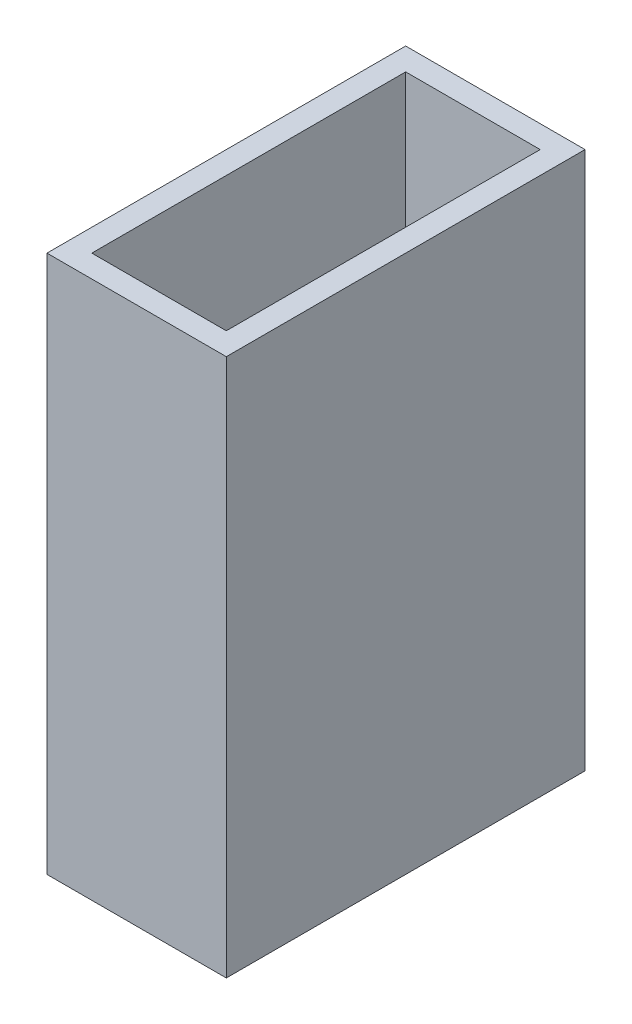
SolidWorks part; units mm, degrees
ref_plane "Front Plane" through (0, 0, 0) normal (0, 0, 1) x (1, 0, 0)
ref_plane "Top Plane" through (0, 0, 0) normal (0, 1, 0) x (1, 0, 0)
ref_plane "Right Plane" through (0, 0, 0) normal (1, 0, 0) x (0, 0, -1)
sketch "Sketch1" plane through (0, 0, 0) normal (0, 1, 0) x (1, 0, 0)
  line L0 (-9.525, -22.225) -> (-9.525, 22.225)
  line L1 (-12.7, -25.4) -> (12.7, -25.4)
  line L2 (-12.7, -25.4) -> (-12.7, 25.4)
  line L3 (-12.7, 25.4) -> (12.7, 25.4)
  line L4 (12.7, -25.4) -> (12.7, 25.4)
  line L5 (-12.7, -25.4) -> (12.7, 25.4) construction
  line L6 (-12.7, 25.4) -> (12.7, -25.4) construction
  line L7 (-9.525, 22.225) -> (9.525, 22.225)
  line L8 (9.525, -22.225) -> (9.525, 22.225)
  line L9 (-9.525, -22.225) -> (9.525, -22.225)
  point P0 (0, 0)
  dimension "D1" = 25.4
  dimension "D2" = 50.8
  dimension "D3" = 3.175
extrude "Boss-Extrude1" add sketch "Sketch1" along normal blind 76.2
